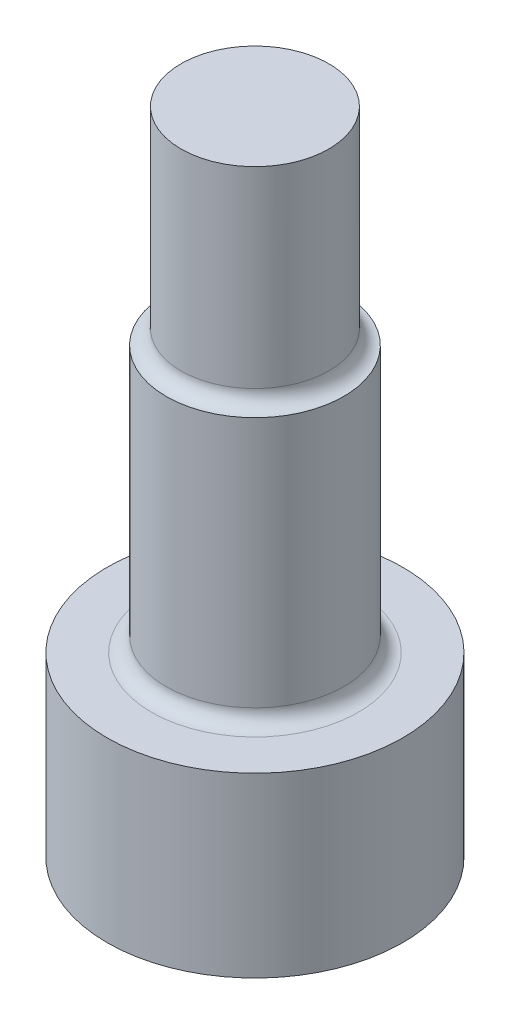
SolidWorks part; units mm, degrees
material "Chrome Stainless Steel"
ref_plane "Front Plane" through (0, 0, 0) normal (0, 0, 1) x (1, 0, 0)
ref_plane "Top Plane" through (0, 0, 0) normal (0, 1, 0) x (1, 0, 0)
ref_plane "Right Plane" through (0, 0, 0) normal (1, 0, 0) x (0, 0, -1)
sketch "Sketch1" plane through (0, 0, 0) normal (0, 0, 1) x (1, 0, 0)
  line L0 (0, 0) -> (5, 0)
  line L1 (55, 0) -> (-55, 0) construction
  line L2 (5, 0) -> (5, 6)
  line L3 (5, 6) -> (3, 6)
  line L4 (3, 6) -> (3, 15)
  line L5 (3, 15) -> (2.5, 15)
  line L6 (0, -55) -> (0, 55) construction
  line L7 (0, 22) -> (0, 0)
  line L8 (2.5, 15) -> (2.5, 22)
  line L9 (2.5, 22) -> (0, 22)
  dimension "D1" = 6
  dimension "D2" = 5
  dimension "D3" = 3
  dimension "D4" = 2.5
  dimension "D5" = 16
  dimension "D6" = 7
revolve "Revolve1" add sketch "Sketch1" angle 360 about L7
sketch "Sketch2" plane through (0, 0, 0) normal (0, -1, 0) x (1, 0, 0)
  line L1 (0, -2.8868) -> (2.5, -1.4434)
  line L2 (2.5, -1.4434) -> (2.5, 1.4434)
  line L3 (2.5, 1.4434) -> (0, 2.8868)
  line L4 (0, 2.8868) -> (-2.5, 1.4434)
  line L5 (-2.5, 1.4434) -> (-2.5, -1.4434)
  line L6 (-2.5, -1.4434) -> (0, -2.8868)
  circle A0 centre (0, 0) radius 2.5 construction
  dimension "D1" = 5
extrude "Cut-Extrude1" cut sketch "Sketch2" against normal blind 2
fillet "Fillet1" radius 0.5 1 edges at (0, 6, 3)
fillet "Fillet2" radius 0.5 1 edges at (0, 15, 2.5)
